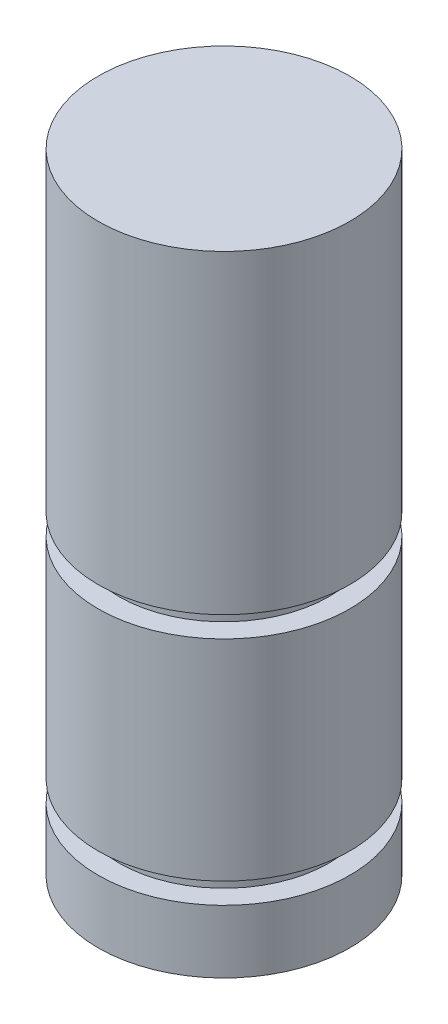
SolidWorks part; units mm, degrees
ref_plane "Front Plane" through (0, 0, 0) normal (0, 0, 1) x (1, 0, 0)
ref_plane "Top Plane" through (0, 0, 0) normal (0, 1, 0) x (1, 0, 0)
ref_plane "Right Plane" through (0, 0, 0) normal (1, 0, 0) x (0, 0, -1)
sketch "Sketch1" plane through (0, 0, 0) normal (0, 1, 0) x (1, 0, 0)
  circle A0 centre (0, 0) radius 6
  dimension "D1" = 12
extrude "Boss-Extrude1" add sketch "Sketch1" along normal blind 30 contours A0
sketch "Sketch2" plane through (0, 0, 0) normal (0, -1, 0) x (1, 0, 0)
  circle A0 centre (0, 0) radius 2.1
  dimension "D1" = 4.2
extrude "Cut-Extrude1" cut sketch "Sketch2" against normal blind 10
ref_plane "Plane1" through (0, 14, 0) normal (0, -1, 0) x (-1, 0, 0)
ref_plane "Plane2" through (0, 4, 0) normal (0, -1, 0) x (-1, 0, 0)
sketch "Sketch3" plane through (0, 14, 0) normal (0, -1, 0) x (-1, 0, 0)
  circle A0 centre (0, 0) radius 6 construction
  circle A1 centre (0, 0) radius 6
  circle A2 centre (0, 0) radius 5
  dimension "D1" = 1
extrude "Cut-Extrude2" cut sketch "Sketch3" against normal blind 1
sketch "Sketch4" plane through (0, 4, 0) normal (0, -1, 0) x (-1, 0, 0)
  circle A0 centre (0, 0) radius 6 construction
  circle A1 centre (0, 0) radius 6
  circle A2 centre (0, 0) radius 5
  dimension "D1" = 10
extrude "Cut-Extrude3" cut sketch "Sketch4" along normal blind 1
